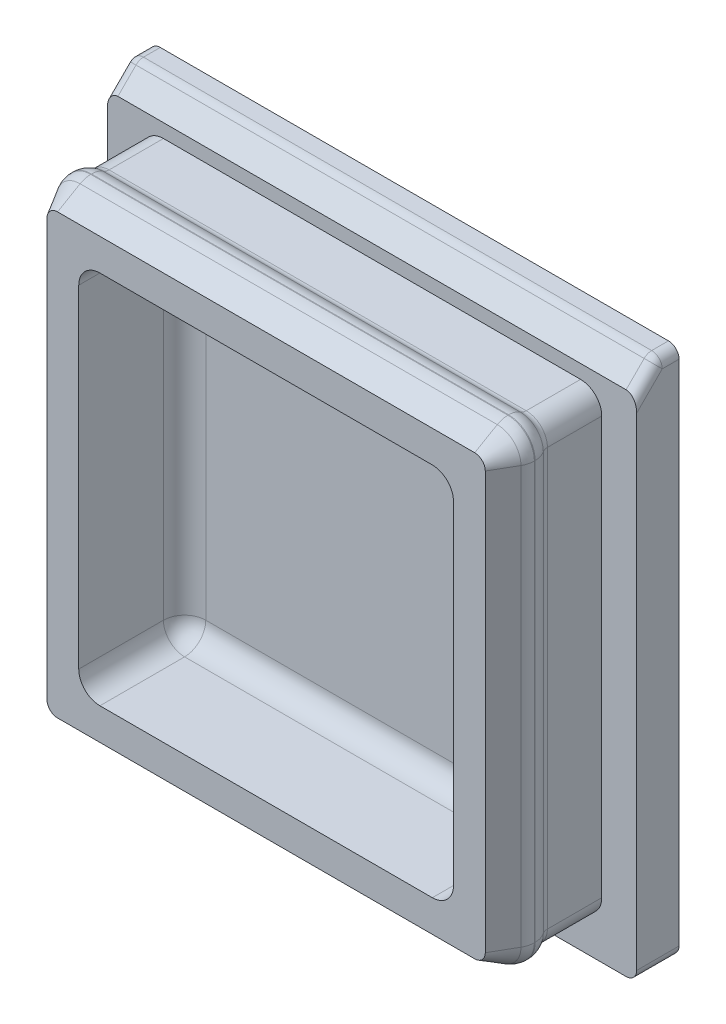
SolidWorks part; units mm, degrees
ref_plane "Ebene vorne" through (0, 0, 0) normal (0, 0, 1) x (1, 0, 0)
ref_plane "Ebene oben" through (0, 0, 0) normal (0, 1, 0) x (1, 0, 0)
ref_plane "Ebene rechts" through (0, 0, 0) normal (1, 0, 0) x (0, 0, -1)
sketch "Skizze1" plane through (0, 0, 0) normal (0, 0, 1) x (1, 0, 0)
  line L1 (-12.5, -12.5) -> (12.5, -12.5)
  line L2 (-12.5, -12.5) -> (-12.5, 12.5)
  line L3 (-12.5, 12.5) -> (12.5, 12.5)
  line L4 (12.5, -12.5) -> (12.5, 12.5)
  line L5 (-12.5, -12.5) -> (12.5, 12.5) construction
  line L6 (-12.5, 12.5) -> (12.5, -12.5) construction
  point P0 (0, 0)
  dimension "D1" = 25
  dimension "D2" = 25
extrude "Aufsatz-Linear austragen1" add sketch "Skizze1" along normal blind 2
sketch "Skizze2" plane through (0, 0, 2) normal (0, 0, 1) x (1, 0, 0)
  line L8 (10.85, -10.85) -> (10.85, 10.85)
  line L9 (10.85, 10.85) -> (-10.85, 10.85)
  line L10 (-10.85, 10.85) -> (-10.85, -10.85)
  line L11 (-10.85, -10.85) -> (10.85, -10.85)
  line L12 (10.85, -10.85) -> (10.85, 10.85)
  line L13 (10.85, 10.85) -> (-10.85, 10.85)
  line L14 (-10.85, 10.85) -> (-10.85, -10.85)
  line L15 (-10.85, -10.85) -> (10.85, -10.85)
  dimension "D1" = 1.65
extrude "Linear-Austragen-Dünn1" add sketch "Skizze2" along normal blind 5 thin thin type one direction reverse wall 2
fillet "Verrundung1" radius 1 4 edges at (-10.85, 10.85, 4.5) (-10.85, -10.85, 4.5) (10.85, -10.85, 4.5) (10.85, 10.85, 4.5)
sketch "Skizze3" plane through (0, 0, 7) normal (0, 0, 1) x (1, 0, 0)
  line L4 (9.85, 10.85) -> (-9.85, 10.85)
  line L5 (-10.85, 9.85) -> (-10.85, -9.85)
  line L6 (-9.85, -10.85) -> (9.85, -10.85)
  line L7 (10.85, -9.85) -> (10.85, 9.85)
  line L8 (9.85, 10.85) -> (-9.85, 10.85)
  line L9 (-10.85, 9.85) -> (-10.85, -9.85)
  line L10 (-9.85, -10.85) -> (9.85, -10.85)
  line L11 (10.85, -9.85) -> (10.85, 9.85)
  arc A4 (-9.85, 10.85) -> (-10.85, 9.85) centre (-9.85, 9.85) ccw
  arc A5 (-10.85, -9.85) -> (-9.85, -10.85) centre (-9.85, -9.85) ccw
  arc A6 (9.85, -10.85) -> (10.85, -9.85) centre (9.85, -9.85) ccw
  arc A7 (10.85, 9.85) -> (9.85, 10.85) centre (9.85, 9.85) ccw
  arc A8 (-9.85, 10.85) -> (-10.85, 9.85) centre (-9.85, 9.85) ccw
  arc A9 (-10.85, -9.85) -> (-9.85, -10.85) centre (-9.85, -9.85) ccw
  arc A10 (9.85, -10.85) -> (10.85, -9.85) centre (9.85, -9.85) ccw
  arc A11 (10.85, 9.85) -> (9.85, 10.85) centre (9.85, 9.85) ccw
  dimension "D1" = 0
extrude "Linear-Austragen-Dünn2" add sketch "Skizze3" against normal blind 2 thin thin type one direction wall 0.25
chamfer "Fase1" distance 0.75 angle 60 8 edges at (0, -11.1, 7) (10.7339, -10.7339, 7) (-10.7339, -10.7339, 7) (11.1, 0, 7) (-11.1, 0, 7) (10.7339, 10.7339, 7) (-10.7339, 10.7339, 7) (0, 11.1, 7) first distance on face at (0, 0, 7)
fillet "Verrundung2" radius 0.5 8 edges at (10.5571, 10.5571, 5) (10.85, 0, 5) (10.5571, -10.5571, 5) (0, -10.85, 5) (-10.5571, -10.5571, 5) (-10.85, 0, 5) (-10.5571, 10.5571, 5) (0, 10.85, 5)
fillet "Verrundung3" radius 1 16 edges at (10.7339, 10.7339, 5) (11.1, 0, 5) (10.7339, -10.7339, 5) (0, -11.1, 5) (-10.7339, -10.7339, 5) (-11.1, 0, 5) (-10.7339, 10.7339, 5) (-10.7339, 10.7339, 5.701) (-11.1, 0, 5.701) (-10.7339, -10.7339, 5.701) (0, -11.1, 5.701) (10.7339, -10.7339, 5.701) (11.1, 0, 5.701) (10.7339, 10.7339, 5.701) (0, 11.1, 5) (0, 11.1, 5.701)
chamfer "Fase2" distance 1 angle 45 1 edges at (0, 12.5, 2)
fillet "Verrundung5" radius 0.5 1 edges at (0, 12.5, 1)
fillet "Verrundung4" radius 0.5 8 edges at (12.5, 12.5, 0.3964) (-12.5, 12.5, 0.3964) (12.5, -12.5, 1) (-12.5, -12.5, 1) (12.5, 11.9268, 1.5732) (12.5, 12.4619, 0.9842) (-12.5, 11.9268, 1.5732) (-12.5, 12.4619, 0.9842)
fillet "Verrundung6" radius 1 8 edges at (0, 8.85, 2) (8.85, 0, 2) (0, -8.85, 2) (-8.85, 0, 2) (-8.85, -8.85, 4.5) (-8.85, 8.85, 4.5) (8.85, -8.85, 4.5) (8.85, 8.85, 4.5)
